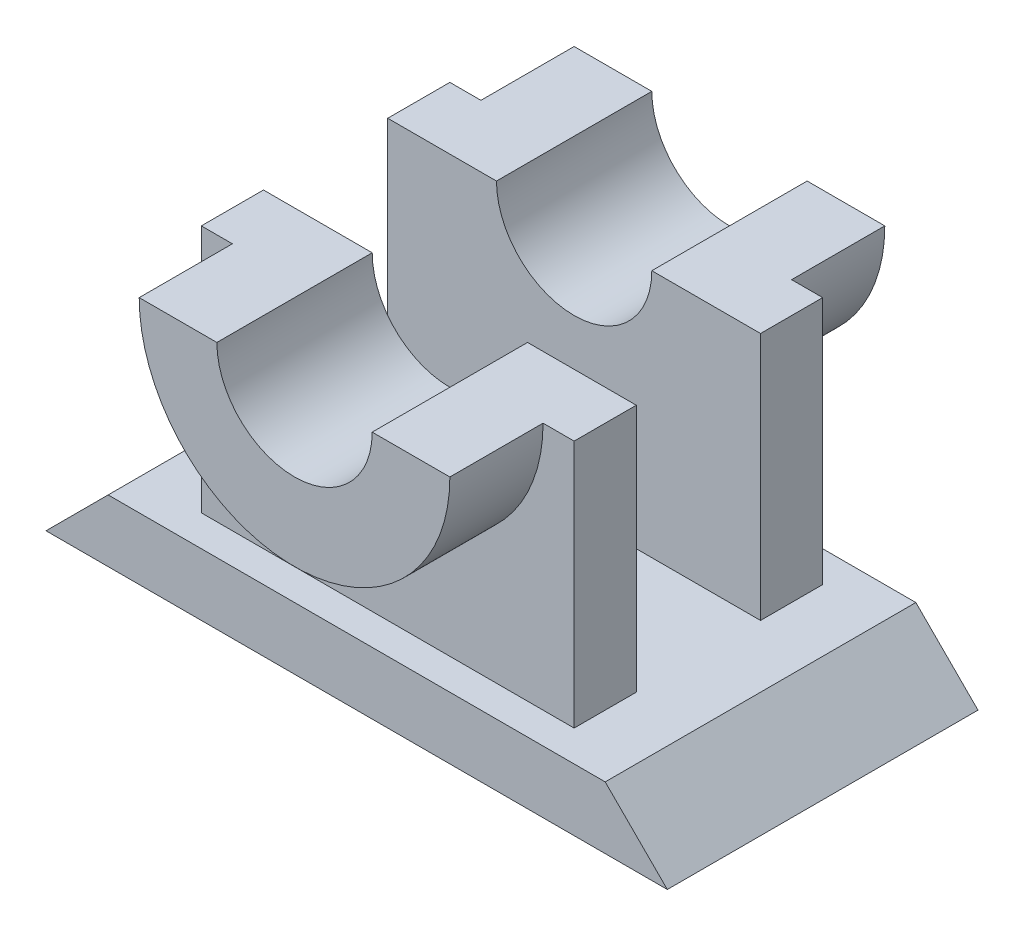
SolidWorks part; units mm, degrees
ref_plane "Front Plane" through (0, 0, 0) normal (0, 0, 1) x (1, 0, 0)
ref_plane "Top Plane" through (0, 0, 0) normal (0, 1, 0) x (1, 0, 0)
ref_plane "Right Plane" through (0, 0, 0) normal (1, 0, 0) x (0, 0, -1)
sketch "Sketch1" plane through (0, 0, 0) normal (0, 0, 1) x (1, 0, 0)
  line L0 (0, 0) -> (100, 0)
  line L1 (100, 0) -> (90, 10)
  line L2 (90, 10) -> (10, 10)
  line L3 (10, 10) -> (0, 0)
  line L4 (20, 10) -> (20, 50)
  line L5 (20, 50) -> (25, 50)
  line L6 (75, 50) -> (80, 50)
  line L7 (80, 50) -> (80, 10)
  line L8 (50, 50) -> (50, -44.5578) construction
  line L9 (37.5, 50) -> (25, 50)
  line L10 (62.5, 50) -> (75, 50)
  arc A0 (37.5, 50) -> (62.5, 50) centre (50, 50) ccw
  arc A1 (25, 50) -> (75, 50) centre (50, 50) ccw
  point P16 (0, 0)
  point P17 (0, 0)
  dimension "D1" = 100
  dimension "D7" = 25
  dimension "D8" = 12.5
  dimension "D2" = 10
  dimension "D3" = 10
  dimension "D4" = 10
  dimension "D5" = 10
  dimension "D6" = 60
  dimension "D9" = 30
  dimension "D10" = 50
extrude "Boss-Extrude1" add sketch "Sketch1" along normal mid plane 50 contours L2 L8 L0 L1 | L8 L2 L3 L0 region at (27.4074, 4.8148, 0) region at (72.5926, 4.8148, 0)
extrude "Boss-Extrude2" add sketch "Sketch1<3>" along normal blind 10 from offset 10 contours A1 L8 L2 L7 L6 | L8 A1 L5 L4 L2 region at (68.0386, 23.5002, 0) region at (31.9614, 23.5002, 0)
sketch "Sketch1<3>" plane through (0, 0, 0) normal (0, 0, 1) x (1, 0, 0) same geometry as "Sketch1"
extrude "Boss-Extrude3" add sketch "Sketch1<4>" against normal blind 10 from offset 10 contours A1 L8 L2 L7 L6 | L8 A1 L5 L4 L2 region at (68.0386, 23.5002, 0) region at (31.9614, 23.5002, 0) offset against normal yes
sketch "Sketch1<4>" plane through (0, 0, 0) normal (0, 0, 1) x (1, 0, 0) same geometry as "Sketch1"
extrude "Boss-Extrude4" add sketch "Sketch1<5>" against normal blind 25 from vertex contours L8 A0 L9 A1 | A0 L8 A1 L10 region at (37.6213, 37.6213, 0) region at (62.3787, 37.6213, 0) starting at point (25, 50, -10)
sketch "Sketch1<5>" plane through (0, 0, 0) normal (0, 0, 1) x (1, 0, 0) same geometry as "Sketch1"
extrude "Boss-Extrude5" add sketch "Sketch1<6>" along normal blind 25 from vertex contours A0 L8 A1 L10 | L8 A0 L9 A1 region at (37.6213, 37.6213, 0) region at (62.3787, 37.6213, 0) starting at point (25, 50, 10)
sketch "Sketch1<6>" plane through (0, 0, 0) normal (0, 0, 1) x (1, 0, 0) same geometry as "Sketch1"
